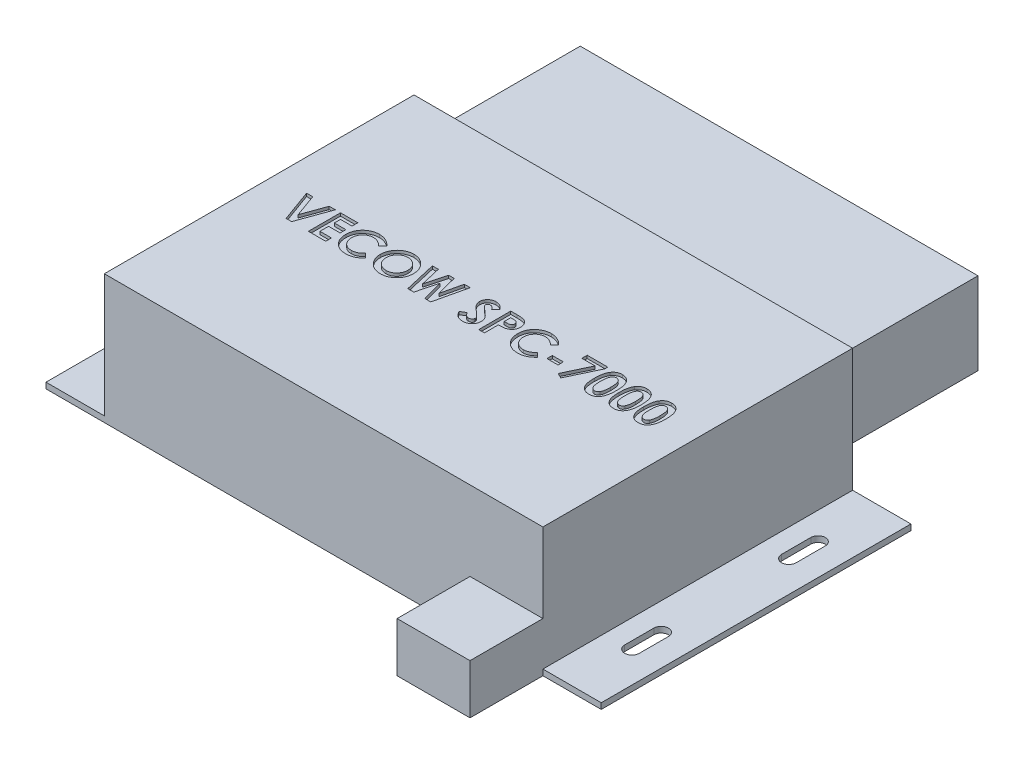
SolidWorks part; units mm, degrees
ref_plane "Front Plane" through (0, 0, 0) normal (0, 0, 1) x (1, 0, 0)
ref_plane "Top Plane" through (0, 0, 0) normal (0, 1, 0) x (1, 0, 0)
ref_plane "Right Plane" through (0, 0, 0) normal (1, 0, 0) x (0, 0, -1)
sketch "Sketch1" plane through (0, 0, 0) normal (0, 1, 0) x (1, 0, 0)
  line L1 (-75.2, 53.1) -> (75.2, 53.1)
  line L2 (-75.2, 53.1) -> (-75.2, -53.1)
  line L3 (-75.2, -53.1) -> (75.2, -53.1)
  line L4 (75.2, 53.1) -> (75.2, -53.1)
  line L5 (-75.2, 53.1) -> (75.2, -53.1) construction
  line L6 (-75.2, -53.1) -> (75.2, 53.1) construction
  point P0 (0, 0)
  dimension "D1" = 150.4
  dimension "D2" = 106.2
extrude "Boss-Extrude1" add sketch "Sketch1" along normal blind 44.2
sketch "Sketch2" plane through (75.2, 0, 0) normal (1, 0, 0) x (0, 0, -1)
  line L0 (53.1, 44.2) -> (53.1, 0) construction
  line L1 (-53.1, 0) -> (53.1, 0)
  line L2 (-53.1, 0) -> (-53.1, 2)
  line L3 (-53.1, 2) -> (53.1, 2)
  line L4 (53.1, 0) -> (53.1, 2)
  dimension "D1" = 2
extrude "Boss-Extrude2" add sketch "Sketch2" along normal blind 20
mirror "Mirror1" about plane through (0, 0, 0) normal (1, 0, 0) of "Boss-Extrude2"
sketch "Sketch3" plane through (0, 0, 0) normal (0, -1, 0) x (1, 0, 0)
  line L0 (-84.55, 31.9) -> (-84.55, 21.9) construction
  line L1 (-82.05, 31.9) -> (-82.05, 21.9)
  line L2 (-87.05, 31.9) -> (-87.05, 21.9)
  line L3 (-84.55, -21.9) -> (-84.55, -31.9) construction
  line L4 (-82.05, -21.9) -> (-82.05, -31.9)
  line L5 (-84.55, 26.9) -> (84.55, 26.9) construction
  line L6 (-84.55, 26.9) -> (-84.55, -26.9) construction
  line L7 (-84.55, -26.9) -> (84.55, -26.9) construction
  line L8 (84.55, 26.9) -> (84.55, -26.9) construction
  line L9 (-84.55, 26.9) -> (84.55, -26.9) construction
  line L10 (-84.55, -26.9) -> (84.55, 26.9) construction
  line L11 (-87.05, -21.9) -> (-87.05, -31.9)
  line L12 (84.55, 31.9) -> (84.55, 21.9) construction
  line L13 (87.05, 31.9) -> (87.05, 21.9)
  line L14 (82.05, 31.9) -> (82.05, 21.9)
  line L15 (84.55, -21.9) -> (84.55, -31.9) construction
  line L16 (87.05, -21.9) -> (87.05, -31.9)
  line L17 (82.05, -21.9) -> (82.05, -31.9)
  arc A0 (-82.05, 31.9) -> (-87.05, 31.9) centre (-84.55, 31.9) ccw
  arc A1 (-87.05, 21.9) -> (-82.05, 21.9) centre (-84.55, 21.9) ccw
  arc A2 (-82.05, -21.9) -> (-87.05, -21.9) centre (-84.55, -21.9) ccw
  arc A3 (-87.05, -31.9) -> (-82.05, -31.9) centre (-84.55, -31.9) ccw
  arc A4 (87.05, 31.9) -> (82.05, 31.9) centre (84.55, 31.9) ccw
  arc A5 (82.05, 21.9) -> (87.05, 21.9) centre (84.55, 21.9) ccw
  arc A6 (87.05, -21.9) -> (82.05, -21.9) centre (84.55, -21.9) ccw
  arc A7 (82.05, -31.9) -> (87.05, -31.9) centre (84.55, -31.9) ccw
  point P0 (0, 0)
  point P7 (-84.55, 26.9)
  point P14 (-84.55, -26.9)
  point P22 (84.55, 26.9)
  point P29 (84.55, -26.9)
  dimension "D3" = 2.5
  dimension "D1" = 169.1
  dimension "D2" = 53.8
  dimension "D4" = 10
extrude "Cut-Extrude1" cut sketch "Sketch3" against normal blind 20
sketch "Sketch4" plane through (0, 44.2, 0) normal (0, 1, 0) x (1, 0, 0)
  line L0 (-75.2, -5.5) -> (75.2, -5.5) construction
  line L1 (-75.2, 53.1) -> (-75.2, -53.1) construction
  line L2 (75.2, 53.1) -> (75.2, -53.1) construction
  text T0 "VECOW SPC-7000" font "Century Gothic" height 11
  dimension "D1" = 5.5
extrude "Cut-Extrude2" cut sketch "Sketch4" against normal blind 1
sketch "Sketch5" plane through (0, 0, -53.1) normal (0, 0, -1) x (-1, 0, 0)
  line L0 (-75.2, 44.2) -> (75.2, 44.2) construction
  line L1 (-68.2, 37.2) -> (68.2, 37.2)
  line L2 (-68.2, 37.2) -> (-68.2, 9)
  line L3 (-68.2, 9) -> (68.2, 9)
  line L4 (68.2, 37.2) -> (68.2, 9)
  line L5 (-68.2, 37.2) -> (68.2, 9) construction
  line L6 (-68.2, 9) -> (68.2, 37.2) construction
  line L7 (-75.2, 44.2) -> (-75.2, 2) construction
  line L8 (75.2, 44.2) -> (75.2, 2) construction
  point P0 (0, 23.1)
  point P7 (0, 44.2)
  point P10 (-75.2, 23.1)
  dimension "D1" = 7
  dimension "D2" = 7
extrude "Boss-Extrude3" add sketch "Sketch5" along normal blind 50
sketch "Sketch6" plane through (0, 0, 53.1) normal (0, 0, 1) x (1, 0, 0)
  line L0 (-95.2, 0) -> (95.2, 0) construction
  line L1 (75.2, 0) -> (50.2, 0)
  line L2 (75.2, 0) -> (75.2, 17)
  line L3 (75.2, 17) -> (50.2, 17)
  line L4 (50.2, 0) -> (50.2, 17)
  point P6 (0, 0)
  dimension "D1" = 25
  dimension "D2" = 17
extrude "Boss-Extrude4" add sketch "Sketch6" along normal blind 25
